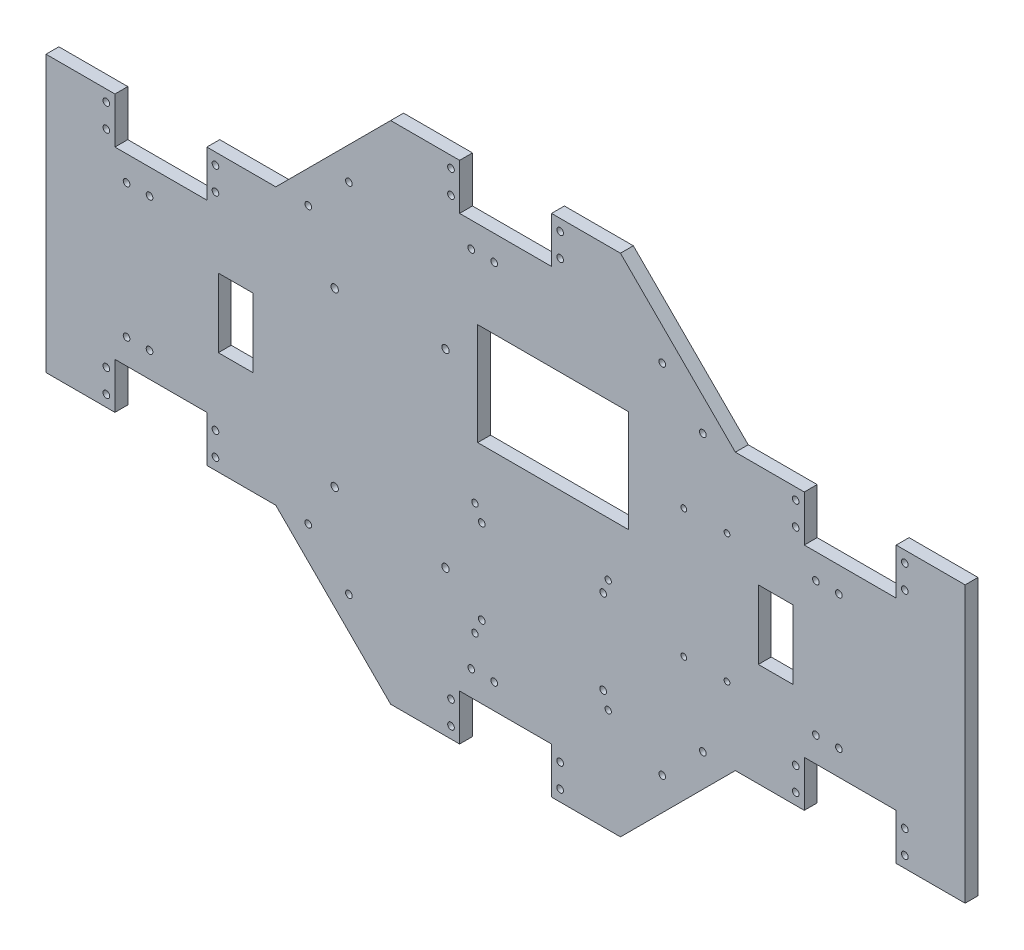
SolidWorks part; units mm, degrees
ref_plane "Front" through (0, 0, 0) normal (0, 0, 1) x (1, 0, 0)
ref_plane "Top" through (0, 0, 0) normal (0, 1, 0) x (1, 0, 0)
ref_plane "Right" through (0, 0, 0) normal (1, 0, 0) x (0, 0, -1)
sketch "Esquisse1" plane through (0, 0, 0) normal (0, 0, 1) x (1, 0, 0)
  line L0 (100, -60) -> (150, -110)
  line L1 (0, 0) -> (25.8386, 0)
  line L2 (0, 0) -> (0, -60)
  line L3 (0, -60) -> (100, -60)
  line L5 (0, 0) -> (100, -60) construction
  line L6 (0, -60) -> (25.8386, 0) construction
  line L7 (150, -110) -> (250, -110)
  line L8 (250, -110) -> (300, -60)
  line L9 (300, -60) -> (400, -60)
  line L10 (400, -60) -> (400, 0)
  line L11 (400, 0) -> (25.8386, 0)
  point P0 (0, 0)
  dimension "D1" = 100
  dimension "D2" = 100
  dimension "D3" = 100
  dimension "D4" = 135
  dimension "D5" = 135
  dimension "D6" = 0
  dimension "D7" = 50
  dimension "D8" = 60
extrude "Boss.-Extru.1" add sketch "Esquisse1" along normal blind 5.6
sketch "Esquisse2" plane through (0, 0, 5.6) normal (0, 0, 1) x (1, 0, 0)
  line L0 (0, -60) -> (100, -60) construction
  line L1 (30, -40) -> (70, -40)
  line L2 (30, -40) -> (30, -60)
  line L3 (30, -60) -> (70, -60)
  line L4 (70, -40) -> (70, -60)
  line L5 (30, -40) -> (70, -60) construction
  line L6 (30, -60) -> (70, -40) construction
  line L7 (0, 0) -> (0, -60) construction
  point P0 (0, -90)
  dimension "D1" = 20
  dimension "D2" = 40
  dimension "D3" = 30
extrude "Enlèv. mat.-Extru.1" cut sketch "Esquisse2" against normal up to next
sketch "Esquisse3" plane through (0, 0, 5.6) normal (0, 0, 1) x (1, 0, 0)
  line L0 (30, -50) -> (70, -50) construction
  line L1 (30, -40) -> (30, -60) construction
  line L2 (70, -60) -> (70, -40) construction
  circle A0 centre (26.25, -55.08) radius 1.45
  circle A1 centre (73.75, -55.08) radius 1.45
  circle A2 centre (73.75, -44.92) radius 1.45
  circle A3 centre (26.25, -44.92) radius 1.45
  circle A4 centre (35.06, -29.09) radius 1.45
  circle A5 centre (45.06, -29.09) radius 1.45
  dimension "D1" = 3.75
  dimension "D2" = 5.08
  dimension "D3" = 47.5
  dimension "D4" = 2.9
  dimension "D5" = 3.75
  dimension "D6" = 2.9
  dimension "D7" = 2.9
  dimension "D8" = 10
  dimension "D9" = 8.81
  dimension "D10" = 15.83
  dimension "D11" = 0
extrude "Enlèv. mat.-Extru.2" cut sketch "Esquisse3" against normal up to next
sketch "Sketch2" plane through (0, 0, 0) normal (0, 0, 1) x (1, 0, 0)
  line L0 (150, -110) -> (250, -110) construction
  line L1 (330, -40) -> (370, -40)
  line L2 (330, -40) -> (330, -60)
  line L3 (330, -60) -> (370, -60)
  line L4 (370, -40) -> (370, -60)
  line L5 (330, -40) -> (370, -60) construction
  line L6 (330, -60) -> (370, -40) construction
  line L7 (300, -60) -> (400, -60) construction
  line L8 (400, -60) -> (400, 0) construction
  line L9 (180, -90) -> (220, -90)
  line L10 (180, -90) -> (180, -110)
  line L11 (180, -110) -> (220, -110)
  line L12 (220, -90) -> (220, -110)
  line L13 (180, -90) -> (220, -110) construction
  line L14 (180, -110) -> (220, -90) construction
  point P0 (0, -90)
  point P11 (-35, 0)
  dimension "D1" = 20
  dimension "D2" = 40
  dimension "D3" = 30
  dimension "D4" = 40
  dimension "D5" = 20
  dimension "D6" = 30
extrude "Cut-Extrude2" cut sketch "Sketch2" against normal through all and the other way through all
sketch "Sketch5" plane through (0, 0, 0) normal (0, 0, 1) x (1, 0, 0)
  line L0 (180, -100) -> (220, -100) construction
  line L1 (220, -110) -> (220, -90) construction
  line L2 (330, -50) -> (370, -50) construction
  line L4 (370, -60) -> (370, -40) construction
  line L5 (330, -40) -> (330, -60) construction
  circle A0 centre (176.25, -105.08) radius 1.45
  circle A1 centre (223.75, -105.08) radius 1.45
  circle A2 centre (223.75, -94.92) radius 1.45
  circle A3 centre (176.25, -94.92) radius 1.45
  circle A4 centre (326.25, -55.08) radius 1.45
  circle A5 centre (373.75, -55.08) radius 1.45
  circle A6 centre (373.75, -44.92) radius 1.45
  circle A7 centre (326.25, -44.92) radius 1.45
  circle A8 centre (185.06, -79.09) radius 1.45
  circle A9 centre (195.06, -79.09) radius 1.45
  circle A10 centre (335.06, -29.09) radius 1.45
  circle A11 centre (345.06, -29.09) radius 1.45
  dimension "D1" = 5.08
  dimension "D2" = 5.08
  dimension "D3" = 47.5
  dimension "D4" = 2.9
  dimension "D5" = 3.75
  dimension "D10" = 2.9
  dimension "D11" = 2.9
  dimension "D12" = 2.9
  dimension "D16" = 2.9
  dimension "D17" = 2.9
  dimension "D6" = 5.08
  dimension "D7" = 5.08
  dimension "D8" = 3.75
  dimension "D9" = 3.75
  dimension "D13" = 10
  dimension "D14" = 8.81
  dimension "D15" = 15.83
  dimension "D18" = 8.81
  dimension "D19" = 15.83
  dimension "D20" = 10
  dimension "D21" = 0
  dimension "D22" = 0
extrude "Cut-Extrude4" cut sketch "Sketch5" along normal through all
mirror "Mirror1" about plane through (0, 0, 0) normal (0, 1, 0) of "Cut-Extrude4", "Cut-Extrude2", "Enlèv. mat.-Extru.1", "Enlèv. mat.-Extru.2", "Boss.-Extru.1"
sketch "Esquisse4" plane through (0, 0, 5.6) normal (0, 0, 1) x (1, 0, 0)
  circle A0 centre (244.6642, -15.882) radius 1.375
  circle A1 centre (186.6642, -15.882) radius 1.375
  circle A2 centre (186.6642, -64.882) radius 1.375
  circle A3 centre (244.6642, -64.882) radius 1.375
  dimension "D1" = 2.75
  dimension "D2" = 2
  dimension "D3" = 24.6642
  dimension "D4" = 74.118
  dimension "D5" = 2
extrude "Enlèv. mat.-Extru.4" cut sketch "Esquisse4" against normal through all
sketch "Esquisse6" plane through (0, 0, 0) normal (0, 0, -1) x (-1, 0, 0)
  circle A0 centre (-242.4775, -21.8213) radius 1.45
  circle A1 centre (-189.6475, -21.8213) radius 1.45
  circle A2 centre (-189.6475, -58.4513) radius 1.45
  circle A3 centre (-242.4775, -58.4513) radius 1.45
  dimension "D1" = 2.9
  dimension "D2" = 2
  dimension "D3" = 68.1787
  dimension "D4" = 22.4775
  dimension "D5" = 2
extrude "Enlèv. mat.-Extru.6" cut sketch "Esquisse6" against normal through all
sketch "Esquisse8" plane through (0, 0, 0) normal (0, 0, -1) x (-1, 0, 0)
  circle A0 centre (-277.5698, 27.6393) radius 1.25
  circle A1 centre (-296.3698, 27.6393) radius 1.25
  circle A2 centre (-296.3698, -28.2607) radius 1.25
  circle A3 centre (-277.5698, -28.2607) radius 1.25
  dimension "D1" = 2.5
  dimension "D2" = 22.4302
  dimension "D3" = 32.3607
  dimension "D4" = 2
  dimension "D5" = 2
extrude "Enlèv. mat.-Extru.7" cut sketch "Esquisse8" against normal through all
sketch "Esquisse9" plane through (0, 0, 0) normal (0, 0, -1) x (-1, 0, 0)
  circle A1 centre (-173.859, -46.6552) radius 1.6
  circle A2 centre (-125.639, -40.2952) radius 1.6
  circle A3 centre (-125.639, 34.5848) radius 1.6
  circle A4 centre (-173.859, 35.8148) radius 1.6
  dimension "D1" = 82.47
  dimension "D2" = 48.22
  dimension "D3" = 1.23
  dimension "D4" = 76.11
  dimension "D5" = 48.22
  dimension "D6" = 6.141
  dimension "D7" = 54.1852
extrude "Enlèv. mat.-Extru.8" cut sketch "Esquisse9" against normal through all
sketch "Esquisse10" plane through (0, 0, 0) normal (0, 0, -1) x (-1, 0, 0)
  line L0 (-253.5582, 7.5532) -> (-253.5582, 52.0032)
  line L1 (-253.5582, 52.0032) -> (-187.8682, 52.0032)
  line L2 (-187.8682, 52.0032) -> (-187.8682, 7.5532)
  line L3 (-187.8682, 7.5532) -> (-253.5582, 7.5532)
  dimension "D1" = 65.69
  dimension "D2" = 44.45
  dimension "D3" = 33.5582
  dimension "D4" = 37.9968
extrude "Enlèv. mat.-Extru.9" cut sketch "Esquisse10" against normal through all
sketch "Esquisse11" plane through (0, 0, 0) normal (0, 0, -1) x (-1, 0, 0)
  line L1 (-310, 15) -> (-325, 15)
  line L2 (-310, 15) -> (-310, -15)
  line L3 (-310, -15) -> (-325, -15)
  line L4 (-325, 15) -> (-325, -15)
  line L5 (-75, 15) -> (-90, 15)
  line L6 (-75, 15) -> (-75, -15)
  line L7 (-75, -15) -> (-90, -15)
  line L8 (-90, 15) -> (-90, -15)
  dimension "D1" = 15
  dimension "D2" = 15
  dimension "D3" = 75
  dimension "D4" = 75
  dimension "D5" = 30
  dimension "D6" = 30
  dimension "D7" = 45
  dimension "D8" = 45
extrude "Enlèv. mat.-Extru.10" cut sketch "Esquisse11" against normal through all
ref_plane "Plan1" through (200, 0, 0) normal (-1, 0, 0) x (0, 0, 1)
ref_plane "Plan2" through (0, 0, 0) normal (0, 1, 0) x (1, 0, 0)
sketch "Esquisse12" plane through (0, 0, 5.6) normal (0, 0, 1) x (1, 0, 0)
  line L1 (200, 24.0954) -> (200, -24.0954) construction
  line L2 (22.5792, 0) -> (-22.5792, 0) construction
  line L3 (100, 60) -> (150, 110) construction
  circle A0 centre (131.8198, 77.6777) radius 1.45
  circle A1 centre (114.1421, 60) radius 1.45
  circle A2 centre (285.8579, 60) radius 1.45
  circle A3 centre (268.1802, 77.6777) radius 1.45
  circle A4 centre (285.8579, -60) radius 1.45
  circle A5 centre (268.1802, -77.6777) radius 1.45
  circle A6 centre (131.8198, -77.6777) radius 1.45
  circle A7 centre (114.1421, -60) radius 1.45
  point P4 (0, 0)
  dimension "D1" = 2.9
  dimension "D2" = 2.9
  dimension "D3" = 25
  dimension "D4" = 10
  dimension "D5" = 14.1421
  dimension "D6" = 0
extrude "Enlèv. mat.-Extru.11" cut sketch "Esquisse12" against normal through all
